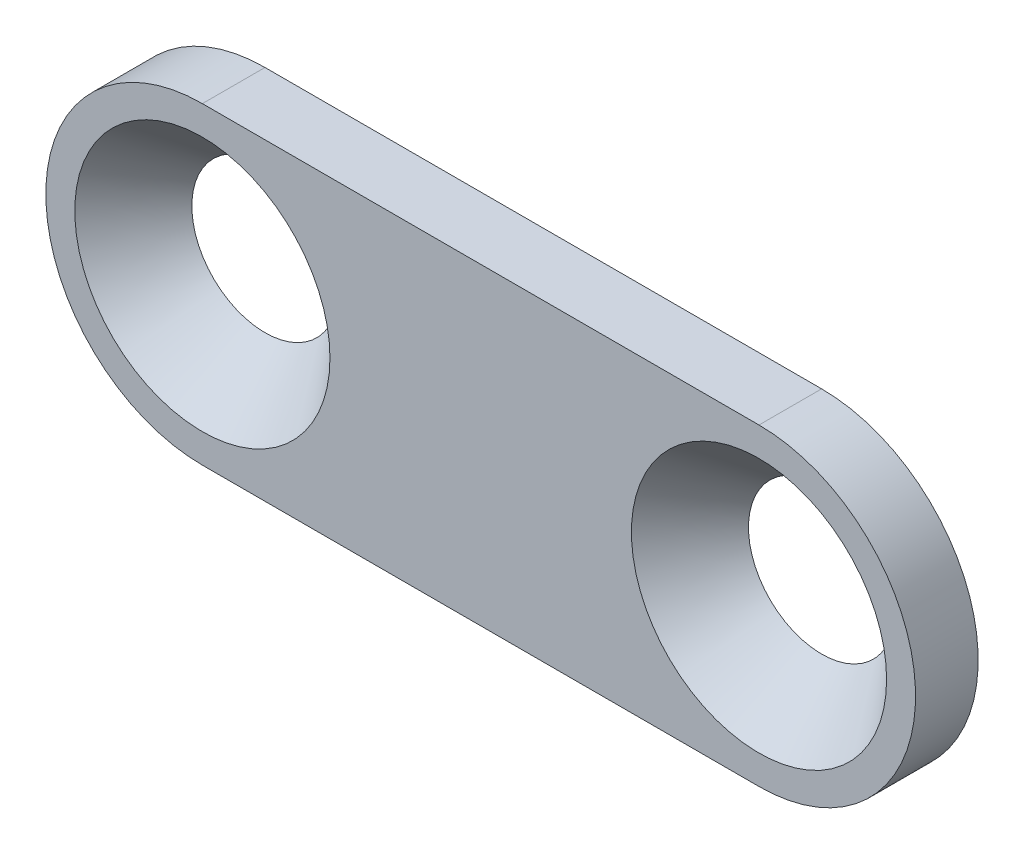
SolidWorks part; units mm, degrees
material "5052-H32"
ref_plane "Front Plane" through (0, 0, 0) normal (0, 0, 1) x (1, 0, 0)
ref_plane "Top Plane" through (0, 0, 0) normal (0, 1, 0) x (1, 0, 0)
ref_plane "Right Plane" through (0, 0, 0) normal (1, 0, 0) x (0, 0, -1)
sketch "Sketch1" plane through (0, 0, 0) normal (0, 0, 1) x (1, 0, 0)
  line L0 (-10.16, 0) -> (10.16, 0) construction
  line L1 (10.16, -5.715) -> (-10.16, -5.715)
  line L3 (10.16, 5.715) -> (-10.16, 5.715)
  line L7 (-10.16, 5.715) -> (-10.16, 5.2197) construction
  circle A0 centre (-10.16, 0) radius 5.2197 construction
  circle A1 centre (10.16, 0) radius 5.2197 construction
  arc A2 (-10.16, 5.715) -> (-10.16, -5.715) centre (-10.16, 0) ccw
  arc A3 (10.16, -5.715) -> (10.16, 5.715) centre (10.16, 0) ccw
  point P0 (0, 0)
  dimension "D2" = 10.4394
  dimension "D1" = 20.32
  dimension "D3" = 11.43
sheet metal parameters "Sheet-Metal1" thickness 2.286 parameters "D1"=0.7366
base flange "Base-Flange1" sketch "Sketch1" thickness 2.286 reverse thickness direction no parameters "D1"=0.7366
hole_wizard "CSK for #8 Flat Head Machine Screw1" positions "Sketch5" profile "Sketch4" countersink size "#8" standard "ANSI Inch" end condition through all
sketch "Sketch5" plane through (0, 0, 0) normal (0, 0, 1) x (1, 0, 0)
  point P0 (-10.16, 0)
  point P2 (10.16, 0)
sketch "Sketch4" plane through (-10.16, 0, 0) normal (1, 0, 0) x (0, -1, 0)
  line L0 (0, 0) -> (0, 2.286)
  line L1 (0, 2.286) -> (2.2479, 2.286)
  line L2 (2.2479, 2.286) -> (2.2479, 2.7725)
  line L3 (2.2479, 2.7725) -> (4.658, 0)
  line L5 (4.658, 0) -> (0, 0)
  line L6 (-2.2479, 2.7725) -> (-4.658, 0) construction
  line L11 (0, -6.35) -> (0, 107.95) construction
  dimension "Thru Hole Dia." = 4.4958
  dimension "Thru Hole Depth" = 2.286
  dimension "Near C'Sink Dia." = 9.316
  dimension "Near C'Sink Angle" = 82
flat pattern "Flat-Pattern1" [suppressed]
sketch "Bend-Lines1" plane through (0, 0, 0) normal (0, 1, 0) x (1, 0, 0)
sketch3d "Bounding-Box1" [suppressed]
  line L0 (-26.035, -5.715, 0) -> (5.715, -5.715, 0) construction
  line L1 (-26.035, 5.715, 0) -> (5.715, 5.715, 0) construction
  line L2 (-26.035, -5.715, 0) -> (-26.035, 5.715, 0) construction
  line L3 (5.715, -5.715, 0) -> (5.715, 5.715, 0) construction
sketch "Sketch6" [suppressed] plane through (0, 0, 0) normal (0, 0, 1) x (1, 0, 0)
  line L1 (-20.4974, -5.6625) -> (-25.2693, -5.6625)
  line L2 (-20.4974, -5.6625) -> (-20.4974, -1.2779)
  line L3 (-20.4974, -1.2779) -> (-25.2693, -1.2779)
  line L4 (-25.2693, -5.6625) -> (-25.2693, -1.2779)
  line L5 (-20.4974, -5.6625) -> (-25.2693, -1.2779) construction
  line L6 (-20.4974, -1.2779) -> (-25.2693, -5.6625) construction
  point P4 (-22.8834, -3.4702)
extrude "Boss-Extrude1" [suppressed] add sketch "Sketch6" against normal up to surface (2.286 mm away) separate body
sketch "Sketch7" [suppressed] plane through (0, 0, -2.286) normal (0, 0, -1) x (-1, 0, 0)
  line L0 (8.1426, -5.715) -> (-7.0974, -5.715)
  line L1 (8.1426, -5.715) -> (8.1426, -9.0275)
  line L2 (-7.0974, -5.715) -> (-7.0974, -9.0275)
  line L3 (8.1426, -9.0275) -> (-7.0974, -9.0275)
  line L4 (10.16, -5.715) -> (-10.16, -5.715) construction
  line L5 (-6.814, 5.715) -> (8.426, 5.715)
  line L6 (-6.814, 5.715) -> (-6.814, 9.7062)
  line L7 (8.426, 5.715) -> (8.426, 9.7062)
  line L8 (-6.814, 9.7062) -> (8.426, 9.7062)
  line L9 (-10.16, 5.715) -> (10.16, 5.715) construction
  dimension "D1" = 15.24
extrude "Boss-Extrude2" [suppressed] add sketch "Sketch7" against normal blind 1.27
sketch "Sketch8" [suppressed] plane through (0, 0, -2.286) normal (0, 0, -1) x (-1, 0, 0)
  circle A0 centre (-10.16, 0) radius 2.45
  circle A1 centre (10.16, 0) radius 2.45
  dimension "D1" = 4.9
extrude "Boss-Extrude3" [suppressed] add sketch "Sketch8" against normal blind 1.27 separate body
